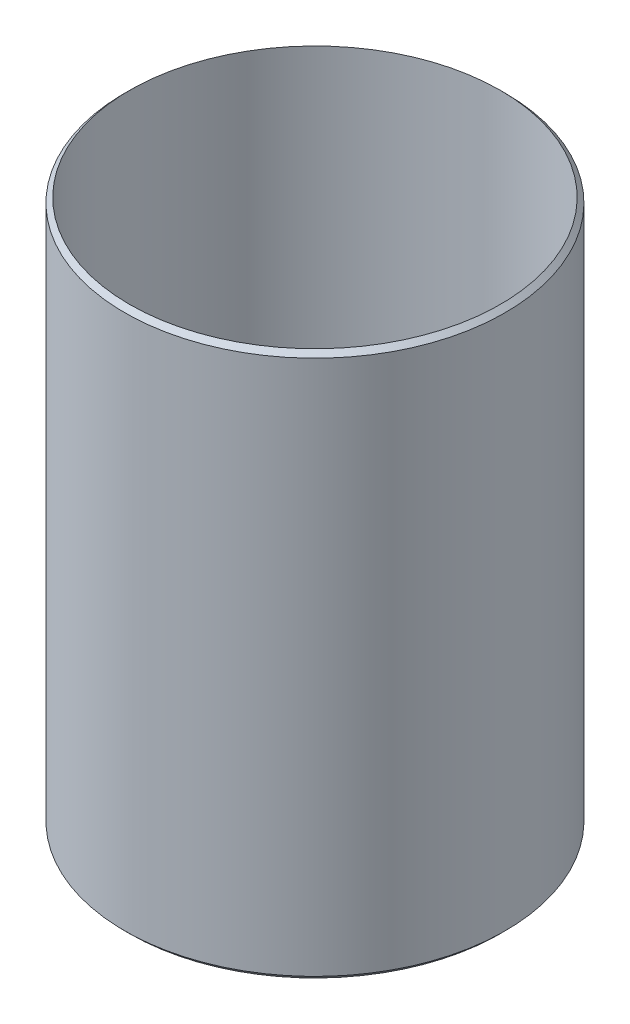
SolidWorks part; units mm, degrees
material "Plain Carbon Steel"
ref_plane "Front Plane" through (0, 0, 0) normal (0, 0, 1) x (1, 0, 0)
ref_plane "Top Plane" through (0, 0, 0) normal (0, 1, 0) x (1, 0, 0)
ref_plane "Right Plane" through (0, 0, 0) normal (1, 0, 0) x (0, 0, -1)
sketch "Sketch1" plane through (0, 0, 0) normal (0, 1, 0) x (1, 0, 0)
  circle A0 centre (0, 0) radius 77.375
  circle A1 centre (0, 0) radius 79.375
  dimension "D1" = 158.75
  dimension "D2" = 2
extrude "Boss-Extrude1" add sketch "Sketch1" along normal blind 227.4
chamfer "Chamfer1" distance 2 angle 45 2 edges at (0, 0, 79.375) (0, 227.4, 79.375)
equation "\"TubeDiameter\" = 6.250in"
equation "\"D1@Sketch1\"=\"TubeDiameter\""
